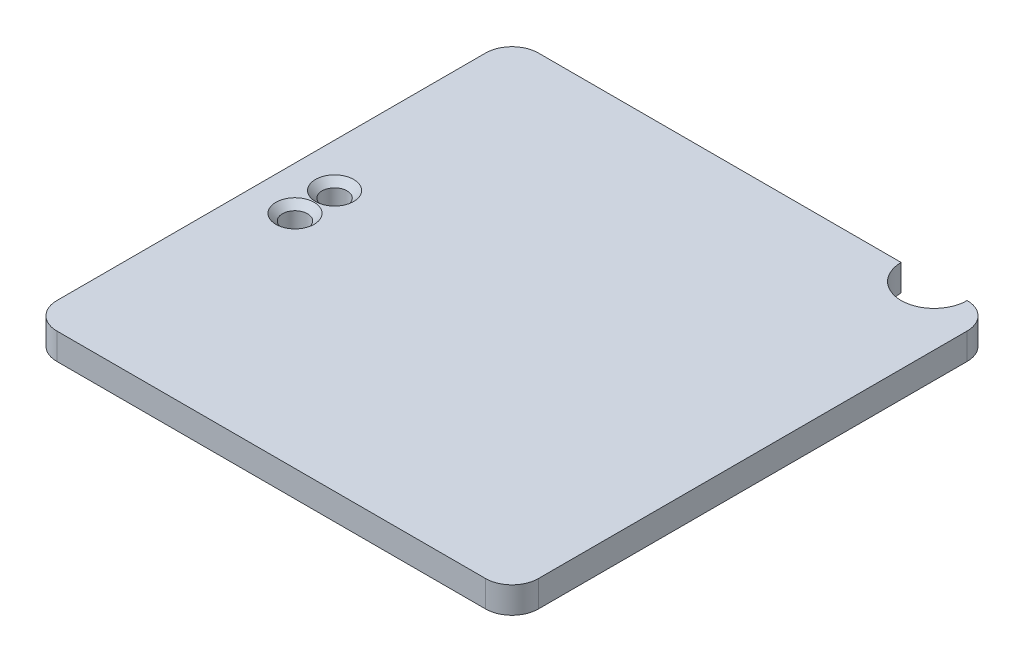
SolidWorks part; units mm, degrees
ref_plane "Front Plane" through (0, 0, 0) normal (0, 0, 1) x (1, 0, 0)
ref_plane "Top Plane" through (0, 0, 0) normal (0, 1, 0) x (1, 0, 0)
ref_plane "Right Plane" through (0, 0, 0) normal (1, 0, 0) x (0, 0, -1)
sketch "Sketch1" plane through (0, 0, 0) normal (0, 1, 0) x (1, 0, 0)
  line L0 (-32.5, -36.5) -> (32.5, -36.5)
  line L1 (-32.5, -37.5) -> (32.5, -37.5)
  line L2 (-37.5, -32.5) -> (-37.5, 32.5)
  line L3 (-32.5, 37.5) -> (32.5, 37.5)
  line L4 (37.5, -32.5) -> (37.5, 32.5)
  line L5 (-37.5, -37.5) -> (37.5, 37.5) construction
  line L6 (-37.5, 37.5) -> (37.5, -37.5) construction
  line L7 (36.5, -32.5) -> (36.5, 32.5)
  line L8 (-32.5, 36.5) -> (32.5, 36.5)
  line L9 (-36.5, -32.5) -> (-36.5, 32.5)
  line L10 (-38.2071, -36.7929) -> (36.7929, 38.2071)
  line L11 (-36.7929, 38.2071) -> (38.2071, -36.7929)
  arc A0 (32.5, -37.5) -> (37.5, -32.5) centre (32.5, -32.5) ccw
  arc A1 (-32.5, -37.5) -> (-37.5, -32.5) centre (-32.5, -32.5) cw
  arc A2 (32.5, 37.5) -> (37.5, 32.5) centre (32.5, 32.5) cw
  arc A3 (-37.5, 32.5) -> (-32.5, 37.5) centre (-32.5, 32.5) cw
  arc A4 (32.5, -36.5) -> (36.5, -32.5) centre (32.5, -32.5) ccw
  arc A5 (32.5, 36.5) -> (36.5, 32.5) centre (32.5, 32.5) cw
  arc A6 (-36.5, 32.5) -> (-32.5, 36.5) centre (-32.5, 32.5) cw
  arc A7 (-32.5, -36.5) -> (-36.5, -32.5) centre (-32.5, -32.5) cw
  point P0 (0, 0)
  dimension "D2" = 5
  dimension "D1" = 75
  dimension "D3" = 1
extrude "Boss-Extrude1" add sketch "Sketch1" along normal mid plane 14 contours A7 L10 L11 A6 L9 | A6 L11 L10 A5 L8 | A5 L10 L11 A4 L7 | A7 L0 A4 L11 L10 region at (0, 0, 23.796) region at (-24.2946, 0, -1.3265) region at (24.2946, 0, -1.3265) region at (0, 0, -24.795)
sketch "Sketch2" plane through (0, -7, 0) normal (0, -1, 0) x (1, 0, 0)
  line L0 (-36.5, 32.5) -> (-36.5, -32.5) construction
  line L1 (-33.5, -33.5) -> (18.5, -33.5)
  line L2 (-33.5, -33.5) -> (-33.5, 33.5)
  line L3 (-33.5, 33.5) -> (18.5, 33.5)
  line L4 (18.5, -33.5) -> (18.5, 33.5)
  line L5 (-26.4, 33.5) -> (-26.4, -33.5)
  line L6 (18.5, 33.5) -> (18.5, 36.5)
  line L7 (-32.5, 36.5) -> (32.5, 36.5) construction
  line L8 (18.5, -33.5) -> (18.5, -36.5)
  line L9 (-32.5, -36.5) -> (32.5, -36.5) construction
  line L10 (-33.5, 7.5) -> (-35.5, 7.5)
  line L11 (-35.5, 7.5) -> (-35.5, -7.5)
  line L12 (-35.5, -7.5) -> (-33.5, -7.5)
  arc M6 (36.5, 32.5) -> (32.5, 36.5) centre (32.5, 32.5) ccw
  line M7 (32.5, 36.5) -> (-32.5, 36.5)
  line M11 (-32.5, -36.5) -> (32.5, -36.5)
  arc M12 (32.5, -36.5) -> (36.5, -32.5) centre (32.5, -32.5) ccw
  line M13 (36.5, -32.5) -> (36.5, 32.5)
  dimension "D1" = 3
  dimension "D2" = 67
  dimension "D3" = 33.5
  dimension "D4" = 52
  dimension "D5" = 7.1
  dimension "D6" = 15
  dimension "D7" = 7.5
  dimension "D8" = 1
extrude "Cut-Extrude1" cut sketch "Sketch2" against normal blind 10 contours L3 L5 L1 L4 | L4 L8 L6 M11 M12 M13 M6 M7 region at (-3.95, -7, 0) region at (27.4574, -7, 0)
sketch "Sketch3" plane through (0, -7, 0) normal (0, -1, 0) x (1, 0, 0)
  line L0 (-33.5, -33.5) -> (-33.5, 33.5) construction
  circle A0 centre (-29.9, 3) radius 1.9
  circle A1 centre (-29.9, -3) radius 1.9
  point P4 (0, 0)
  dimension "D1" = 3.8
  dimension "D2" = 3.6
  dimension "D3" = 3
  dimension "D4" = 3
extrude "Cut-Extrude2" cut sketch "Sketch3" against normal through all
chamfer "Chamfer1" distance 1 angle 45 2 edges at (-29.9, 7, 1.1) (-29.9, 7, -4.9)
extrude "Cut-Extrude5" cut sketch "Sketch2<3>" against normal blind 4 contours L5 L3 L2 L1 | L11 L12 L2 L10 region at (-29.95, -7, 0) region at (-34.5, -7, 0)
sketch "Sketch2<3>" plane through (0, -7, 0) normal (0, -1, 0) x (1, 0, 0) same geometry as "Sketch2"
sketch "Sketch6" plane through (0, 7, 0) normal (0, 1, 0) x (1, 0, 0)
  line L8 (34.5, -32.5) -> (34.5, 32.5)
  line L9 (32.5, 34.5) -> (-32.5, 34.5)
  line L10 (-34.5, 32.5) -> (-34.5, -32.5)
  line L11 (-32.5, -34.5) -> (32.5, -34.5)
  line L13 (32.5, 34.5) -> (-32.5, 34.5)
  line L14 (-34.5, 32.5) -> (-34.5, -32.5)
  line L15 (-32.5, -34.5) -> (32.5, -34.5)
  line L16 (34.5, -32.5) -> (34.5, 32.5)
  arc A8 (32.5, -34.5) -> (34.5, -32.5) centre (32.5, -32.5) ccw
  arc A9 (32.5, -34.5) -> (34.5, -32.5) centre (32.5, -32.5) ccw
  arc A10 (-32.5, 34.5) -> (-34.5, 32.5) centre (-32.5, 32.5) ccw
  arc A11 (-34.5, -32.5) -> (-32.5, -34.5) centre (-32.5, -32.5) ccw
  arc A14 (-32.5, 34.5) -> (-34.5, 32.5) centre (-32.5, 32.5) ccw
  arc A15 (-34.5, -32.5) -> (-32.5, -34.5) centre (-32.5, -32.5) ccw
  arc A16 (34.5, 32.5) -> (32.5, 34.5) centre (32.5, 32.5) ccw
  arc A17 (34.5, 32.5) -> (32.5, 34.5) centre (32.5, 32.5) ccw
  dimension "D1" = 2
sketch "Sketch7" plane through (0, -3, 0) normal (0, -1, 0) x (1, 0, 0)
  line L0 (-33.5, 7.5) -> (-33.5, -7.5)
  line M4 (-33.5, 7.5) -> (-35.5, 7.5)
  line M5 (-35.5, 7.5) -> (-35.5, -7.5)
  line M6 (-35.5, -7.5) -> (-33.5, -7.5)
extrude "Boss-Extrude2" add sketch "Sketch7" along normal blind 1 contours L0 M4 M5 M6 region at (-34.5, -3, 0)
sketch "Sketch9" plane through (0, 7, 0) normal (0, 1, 0) x (1, 0, 0)
  line L0 (-32.5, 36.5) -> (32.5, 36.5) construction
  line L1 (36.5, -32.5) -> (36.5, 32.5) construction
  arc A0 (22.5, 36.5) -> (32.5, 36.5) centre (27.5, 36.5) ccw
  point P3 (0, 0)
  line M6 (32.5, 36.5) -> (-32.5, 36.5)
  dimension "D1" = 5
  dimension "D2" = 9
extrude "Cut-Extrude7" cut sketch "Sketch9" against normal through all contours A0 M6 region at (27.5, 7, -34.3779)
sketch "Sketch11" plane through (0, -3, 0) normal (0, -1, 0) x (1, 0, 0)
  line L0 (-33.5, 7.5) -> (-26.4, 7.5)
  line L1 (-26.4, 33.5) -> (-26.4, -33.5) construction
  line L2 (-33.5, -7.5) -> (-26.4, -7.5)
  line M1 (-26.4, 33.5) -> (-33.5, 33.5)
  line M2 (-33.5, 33.5) -> (-33.5, -33.5)
  line M3 (-33.5, -33.5) -> (-26.4, -33.5)
  line M4 (-26.4, -33.5) -> (-26.4, 33.5)
extrude "Cut-Extrude9" cut sketch "Sketch11" against normal blind 6 contours L0 M2 M4 M1 | L2 M2 M3 M4 region at (-29.95, -3, 20.5) region at (-29.95, -3, -20.5)
sketch "Sketch13" plane through (0, -7, 0) normal (0, -1, 0) x (1, 0, 0)
  line L22 (-32.5, -36.5) -> (18.5, -36.5)
  line L23 (18.5, -33.5) -> (-33.5, -33.5)
  line L24 (-33.5, -33.5) -> (-33.5, -7.5)
  line L25 (-33.5, -7.5) -> (-35.5, -7.5)
  line L26 (-35.5, -7.5) -> (-35.5, 7.5)
  line L27 (-35.5, 7.5) -> (-33.5, 7.5)
  line L28 (-33.5, 7.5) -> (-33.5, 33.5)
  line L29 (-33.5, 33.5) -> (18.5, 33.5)
  line L30 (18.5, 33.5) -> (18.5, 36.5)
  line L31 (18.5, 36.5) -> (-32.5, 36.5)
  line L32 (-36.5, 32.5) -> (-36.5, -32.5)
  line L33 (-32.5, -36.5) -> (18.5, -36.5)
  line L34 (18.5, -33.5) -> (-33.5, -33.5)
  line L35 (-33.5, -33.5) -> (-33.5, -7.5)
  line L36 (-33.5, -7.5) -> (-35.5, -7.5)
  line L37 (-35.5, -7.5) -> (-35.5, 7.5)
  line L38 (-35.5, 7.5) -> (-33.5, 7.5)
  line L39 (-33.5, 7.5) -> (-33.5, 33.5)
  line L40 (-33.5, 33.5) -> (18.5, 33.5)
  line L41 (18.5, 33.5) -> (18.5, 36.5)
  line L42 (18.5, 36.5) -> (-32.5, 36.5)
  line L43 (-36.5, 32.5) -> (-36.5, -32.5)
  line L45 (18.5, -36.5) -> (18.5, -33.5)
  line L46 (18.5, -36.5) -> (18.5, -33.5)
  arc A7 (-32.5, 36.5) -> (-36.5, 32.5) centre (-32.5, 32.5) ccw
  arc A8 (-36.5, -32.5) -> (-32.5, -36.5) centre (-32.5, -32.5) ccw
  arc A10 (-32.5, 36.5) -> (-36.5, 32.5) centre (-32.5, 32.5) ccw
  arc A11 (-36.5, -32.5) -> (-32.5, -36.5) centre (-32.5, -32.5) ccw
  dimension "D1" = 0
extrude "Cut-Extrude10" cut sketch "Sketch13" against normal up to surface (10 mm away) up to face at (3.2905, 3, -2.1)
sketch "Sketch15" plane through (0, -3, 0) normal (0, -1, 0) x (1, 0, 0)
  line L0 (-33.5, -33.5) -> (-33.5, 33.5) construction
  line L1 (-26.4, 33.5) -> (-26.4, -33.5) construction
  line L3 (-33.5, -6.05) -> (-26.4, -6.05)
  line L4 (-33.5, -6.05) -> (-33.5, 6.05)
  line L5 (-33.5, 6.05) -> (-26.4, 6.05)
  line L6 (-26.4, -6.05) -> (-26.4, 6.05)
  line L7 (-33.5, -6.05) -> (-26.4, 6.05) construction
  line L8 (-33.5, 6.05) -> (-26.4, -6.05) construction
  point P0 (0, 0)
  point P4 (-29.95, 0)
  line M5 (-33.5, 7.5) -> (-33.5, -7.5)
  line M6 (-33.5, -7.5) -> (-26.4, -7.5)
  line M7 (-26.4, -7.5) -> (-26.4, 7.5)
  dimension "D1" = 12.1
extrude "Boss-Extrude3" add sketch "Sketch15" along normal up to surface (1 mm away) contours L3 M5 M6 M7 region at (-29.95, -3, -6.775) up to face at (-34.5, -4, 0)
sketch "Sketch16" plane through (0, 7, 0) normal (0, 1, 0) x (1, 0, 0)
  line L8 (22.5, 36.5) -> (-32.5, 36.5)
  line L9 (-36.5, 32.5) -> (-36.5, -32.5)
  line L10 (-32.5, -36.5) -> (32.5, -36.5)
  line L11 (36.5, -32.5) -> (36.5, 32.5)
  line L12 (22.5, 36.5) -> (-32.5, 36.5)
  line L13 (-36.5, 32.5) -> (-36.5, -32.5)
  line L14 (-32.5, -36.5) -> (32.5, -36.5)
  line L15 (36.5, -32.5) -> (36.5, 32.5)
  arc A10 (22.5, 36.5) -> (32.5, 36.5) centre (27.5, 36.5) ccw
  arc A11 (-32.5, 36.5) -> (-36.5, 32.5) centre (-32.5, 32.5) ccw
  arc A12 (-36.5, -32.5) -> (-32.5, -36.5) centre (-32.5, -32.5) ccw
  arc A13 (32.5, -36.5) -> (36.5, -32.5) centre (32.5, -32.5) ccw
  arc A14 (36.5, 32.5) -> (32.5, 36.5) centre (32.5, 32.5) ccw
  arc A15 (22.5, 36.5) -> (32.5, 36.5) centre (27.5, 36.5) ccw
  arc A16 (-32.5, 36.5) -> (-36.5, 32.5) centre (-32.5, 32.5) ccw
  arc A17 (-36.5, -32.5) -> (-32.5, -36.5) centre (-32.5, -32.5) ccw
  arc A18 (32.5, -36.5) -> (36.5, -32.5) centre (32.5, -32.5) ccw
  arc A19 (36.5, 32.5) -> (32.5, 36.5) centre (32.5, 32.5) ccw
  dimension "D1" = 0
